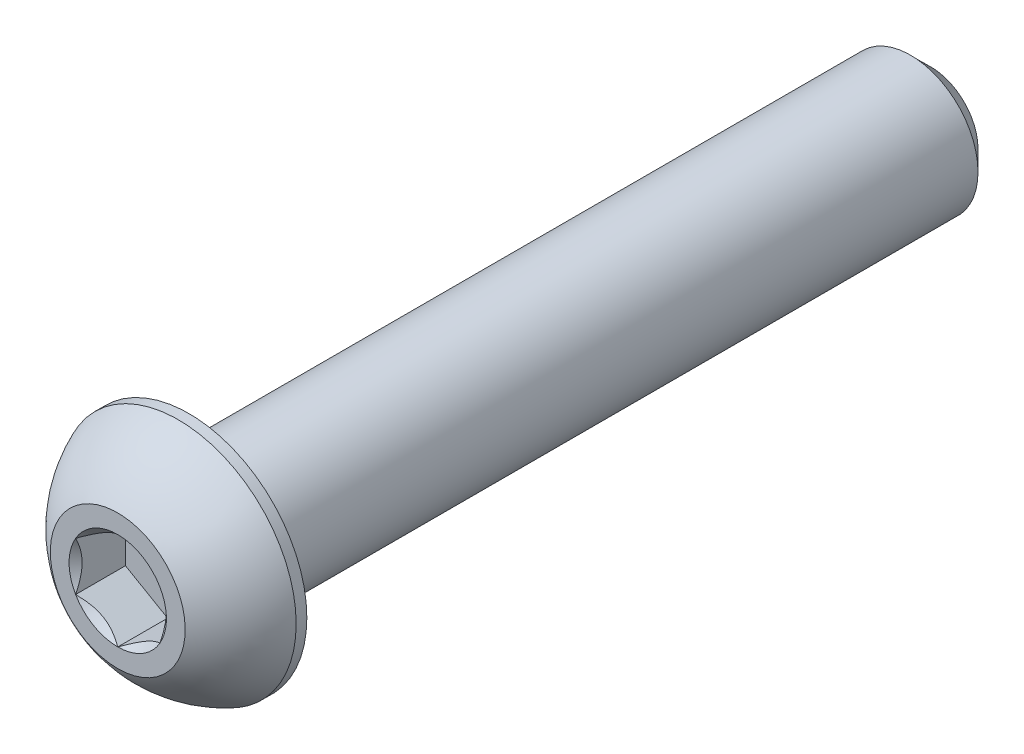
SolidWorks part; units mm, degrees
ref_plane "Front" through (0, 0, 0) normal (0, 0, 1) x (1, 0, 0)
ref_plane "Top" through (0, 0, 0) normal (0, 1, 0) x (1, 0, 0)
ref_plane "Right" through (0, 0, 0) normal (1, 0, 0) x (0, 0, -1)
sketch "Sketch1" plane through (0, 0, 0) normal (1, 0, 0) x (0, 0, -1)
  line L2 (3.3528, 3.175) -> (38.2778, 3.175)
  line L3 (38.2778, 3.175) -> (38.2778, 0)
  line L4 (38.2778, 0) -> (3.3528, 0)
  line L6 (2.8499, 5.5499) -> (3.3528, 5.5499) construction
  line L7 (38.2778, 3.175) -> (38.2778, -3.175) construction
  line L8 (0, 0) -> (3.3528, 0) construction
  line L9 (3.3528, 5.5499) -> (3.3528, -5.5499) construction
  line L11 (3.3528, 3.175) -> (3.3528, 0)
  line L13 (0, 1.9844) -> (0, -1.9844) construction
  line L14 (0, 1.9844) -> (0, 3.175) construction
  arc A3 (0, 3.175) -> (2.8499, 5.5499) centre (5.0603, 0) cw construction
  dimension "D1" = 0.5029
revolve "Revolve1" add sketch "Sketch1" angle 360 mid plane about L4
sketch "Sketch3" plane through (0, 0, -38.2778) normal (0, 0, -1) x (-1, 0, 0)
  circle A0 centre (0, 0) radius 3.175
curve "Helix/Spiral1" [suppressed] pitch 1.27 height 36.195 turns 28.5
sketch "Sketch2" plane through (0, 0, 0) normal (1, 0, 0) x (0, 0, -1)
  line L0 (38.2778, 3.175) -> (39.389, 3.175)
  line L1 (39.389, 3.175) -> (38.9128, 2.3501)
  line L2 (38.9128, 2.3501) -> (38.754, 2.3501)
  line L3 (38.754, 2.3501) -> (38.2778, 3.175)
  line L4 (38.5159, 2.7626) -> (39.1509, 2.7626) construction
  dimension "D1" = 60
  dimension "D2" = 0.1588
  dimension "D3" = 0.635
chamfer "Chamfer1" distance 0.9525 angle 45 1 edges at (0, 3.175, -38.2778)
sweep "Cut-Sweep1" [suppressed] cut profiles "Sketch2" path "Helix/Spiral1"
sketch "Sketch7" plane through (0, 0, 0) normal (1, 0, 0) x (0, 0, -1)
  line L6 (2.8499, 5.5499) -> (3.3528, 5.5499) construction
  line L8 (0, 0) -> (3.3528, 0) construction
  line L11 (3.3528, 5.5499) -> (3.3528, -5.5499) construction
  line L12 (2.8499, 5.5499) -> (3.3528, 5.5499)
  line L13 (0, 0) -> (3.3528, 0)
  line L14 (0, 1.9844) -> (0, -1.9844) construction
  line L15 (3.3528, 5.5499) -> (3.3528, 0)
  line L16 (0, 3.175) -> (0, 0)
  arc A2 (2.8499, 5.5499) -> (0, 3.175) centre (5.0603, 0) ccw construction
  arc A3 (2.8499, 5.5499) -> (0, 3.175) centre (5.0603, 0) ccw
revolve "Revolve2" add sketch "Sketch7" angle 360 mid plane about L13
sketch "Sketch5" plane through (0, 0, 0) normal (0, 0, 1) x (1, 0, 0)
  line L1 (1.9844, -1.1457) -> (1.9844, 1.1457)
  line L2 (1.9844, 1.1457) -> (0, 2.2914)
  line L3 (0, 2.2914) -> (-1.9844, 1.1457)
  line L4 (-1.9844, 1.1457) -> (-1.9844, -1.1457)
  line L5 (-1.9844, -1.1457) -> (0, -2.2914)
  line L6 (0, -2.2914) -> (1.9844, -1.1457)
  circle A0 centre (0, 0) radius 1.9844 construction
extrude "Cut-Extrude2" cut sketch "Sketch5" against normal blind 2.347
sketch "Sketch6" plane through (0, 0, 0) normal (0, 0, 1) x (1, 0, 0)
  circle A0 centre (0, 0) radius 2.2914
extrude "Cut-Extrude3" cut sketch "Sketch6" against normal blind 2.347 draft 45
sketch "Sketch9" [suppressed] plane through (0, 0, -3.3528) normal (0, 0, 1) x (1, 0, 0)
  circle A2 centre (0, 0) radius 3.175
extrude "Boss-Extrude2" [suppressed] add sketch "Sketch9" against normal offset from surface (25.4 mm away) 22.225 up to face at (0, 2.2225, -38.2778)
sketch "Sketch10" [suppressed] plane through (0, 0, 0) normal (1, 0, 0) x (0, 0, -1)
  line L0 (38.2778, 3.175) -> (38.2778, -3.175) construction
  point P0 (36.3728, -3.175)
  dimension "D1" = 1.905
equation "\"D3@Helix/Spiral1\" = \"Lg@Sketch1\" + \"D4@Helix/Spiral1\""
equation "\"D2@Sketch2\" = \"D4@Helix/Spiral1\" * .125"
equation "\"D3@Sketch2\" = \"D4@Helix/Spiral1\" * .5"
equation "\"D1@Chamfer1\" = \"D4@Helix/Spiral1\" * .75"
equation "\"D1@Cut-Extrude2\" = \"Head Ht@Sketch1\" * .7"
equation "\"D1@Sketch1\" = \"Head Ht@Sketch1\" * .15"
equation "\"D1@Sketch10\" = \"D4@Helix/Spiral1\" * 1.5"
equation "\"D1@Cut-Extrude3\" = \"D1@Cut-Extrude2\""
